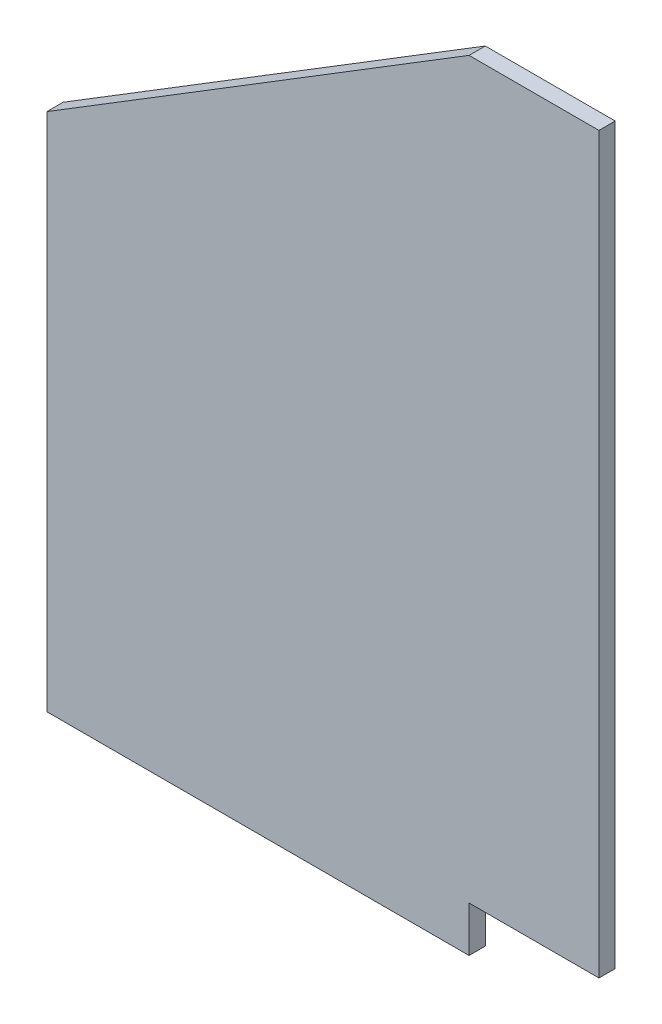
SolidWorks part; units mm, degrees
material "A-Glass Fiber"
ref_plane "Front Plane" through (0, 0, 0) normal (0, 0, 1) x (1, 0, 0)
ref_plane "Top Plane" through (0, 0, 0) normal (0, 1, 0) x (1, 0, 0)
ref_plane "Right Plane" through (0, 0, 0) normal (1, 0, 0) x (0, 0, -1)
sketch "Sketch1" plane through (0, 0, 0) normal (0, 0, 1) x (1, 0, 0)
  line L0 (0, 0) -> (0, 143.51)
  line L1 (0, 143.51) -> (-25.4, 143.51)
  line L3 (-107.95, -8.89) -> (-25.4, -8.89)
  line L4 (-25.4, -8.89) -> (-25.4, 0)
  line L5 (-25.4, 0) -> (0, 0)
  line L6 (-107.95, -8.89) -> (-107.95, 92.71)
  line L7 (-107.95, 92.71) -> (-25.4, 143.51)
  dimension "D1" = 8.89
  dimension "D2" = 82.55
  dimension "D3" = 25.4
  dimension "D4" = 152.4
  dimension "D5" = 25.4
  dimension "D6" = 101.6
extrude "Boss-Extrude1" add sketch "Sketch1" along normal blind 3.175
